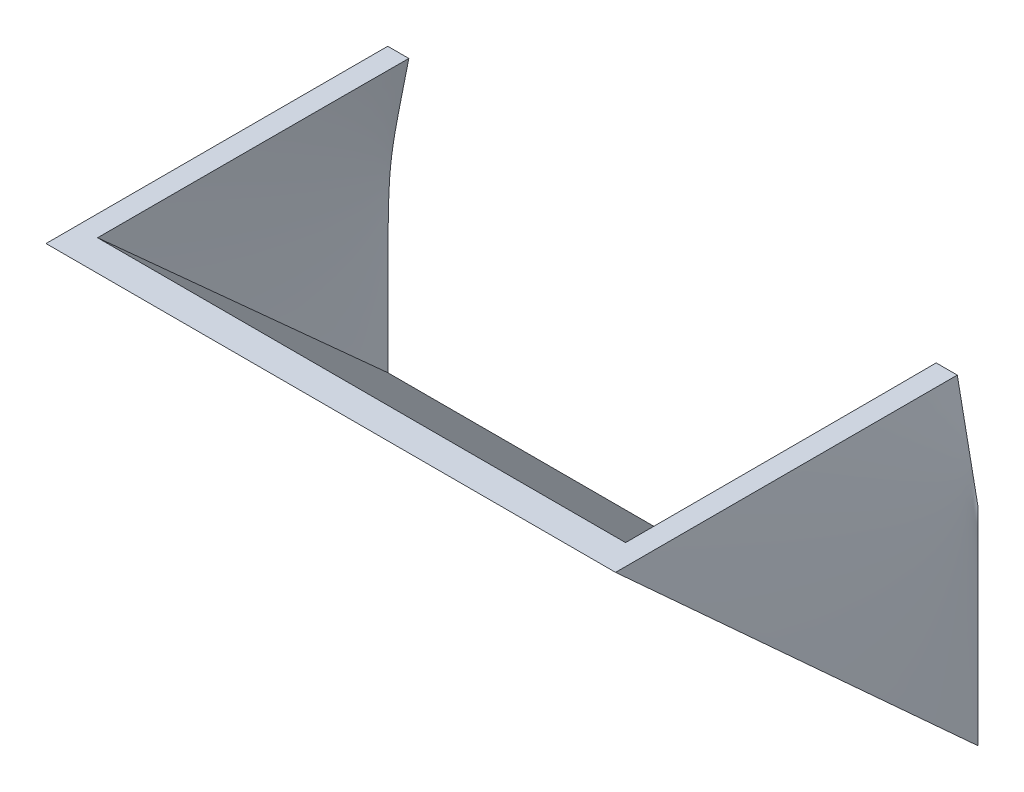
SolidWorks part; units mm, degrees
ref_plane "Plan de face" through (0, 0, 0) normal (0, 0, 1) x (1, 0, 0)
ref_plane "Plan de dessus" through (0, 0, 0) normal (0, 1, 0) x (1, 0, 0)
ref_plane "Plan de droite" through (0, 0, 0) normal (1, 0, 0) x (0, 0, -1)
sketch "Esquisse1" plane through (0, 0, 0) normal (0, 0, 1) x (1, 0, 0)
  line L1 (14.75, -5) -> (-14.75, -5)
  line L2 (14.75, -5) -> (14.75, 5)
  line L3 (14.75, 5) -> (-14.75, 5)
  line L4 (-14.75, -5) -> (-14.75, 5)
  line L5 (14.75, -5) -> (-14.75, 5) construction
  line L6 (14.75, 5) -> (-14.75, -5) construction
  point P0 (0, 0)
  dimension "D1" = 10
  dimension "D2" = 29.5
sketch3d "Esquisse3D1"
  line L0 (0, 0, 0) -> (0, 0, 8.25) construction
  line L1 (0, 0, 8.25) -> (0, 10, 8.25) construction
  line L3 (13.75, 10, 0) -> (13.75, 10, 16.5)
  line L4 (13.75, 10, 0) -> (-13.75, 10, 0)
  line L5 (-13.75, 10, 0) -> (-13.75, 10, 16.5)
  line L6 (13.75, 10, 16.5) -> (-13.75, 10, 16.5)
  line L7 (13.75, 10, 0) -> (-13.75, 10, 16.5) construction
  line L8 (-13.75, 10, 0) -> (13.75, 10, 16.5) construction
  dimension "D1" = 8.25
  dimension "D2" = 10
  dimension "D3" = 16.5
  dimension "D4" = 27.5
loft "Lissage1" add profiles "Esquisse1", "Esquisse3D1" connector at (-14.75, -5, 0) connector at (-13.75, 10, 16.5)
shell "Coque1" thickness 1 removed face at (0, 10, 8.25) removed face at (-4.75, 2.5, 0)
